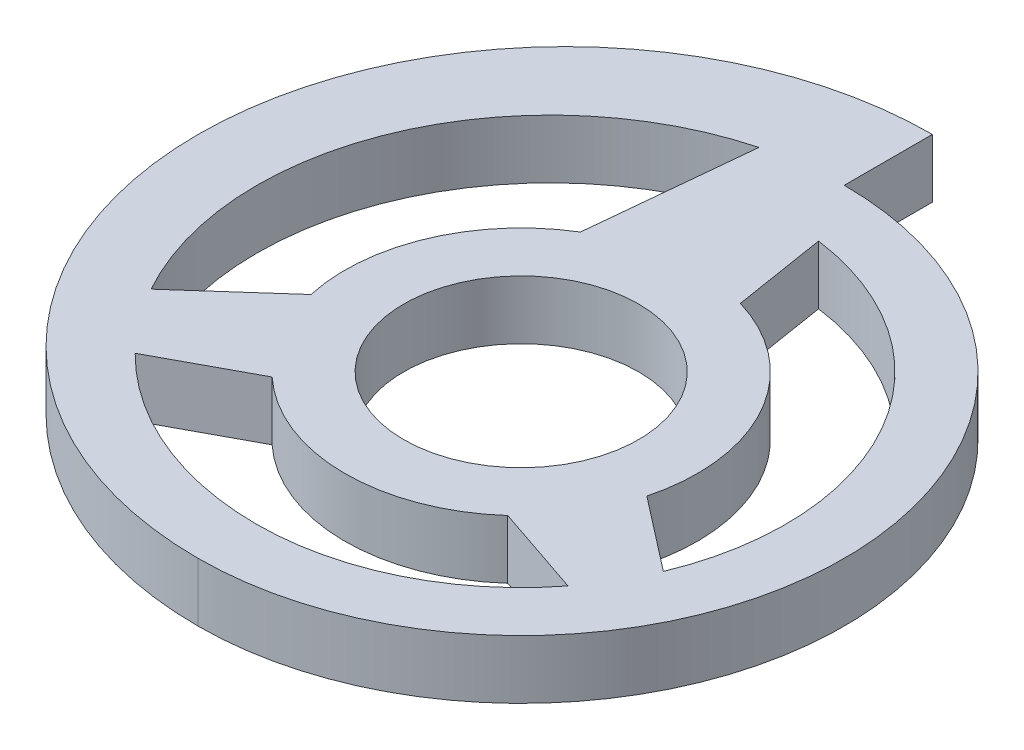
SolidWorks part; units mm, degrees
ref_plane "Front Plane" through (0, 0, 0) normal (0, 0, 1) x (1, 0, 0)
ref_plane "Top Plane" through (0, 0, 0) normal (0, 1, 0) x (1, 0, 0)
ref_plane "Right Plane" through (0, 0, 0) normal (1, 0, 0) x (0, 0, -1)
other "Center of Mass"
sketch "Sketch1" plane through (0, 0, 0) normal (0, 1, 0) x (1, 0, 0)
  line L0 (0, 70) -> (0, 55)
  line L1 (6.0433, 44.5326) -> (8.5696, 28.75)
  line L5 (-35.5895, -30.1196) -> (-20.4365, -21.9624)
  line L6 (-12.8373, 53.3239) -> (-15.5632, 25.6473)
  line L7 (-43.6898, -19.3146) -> (-29.2885, -6.4949)
  line L10 (6.0433, 44.5326) -> (6.0059, 44.5974)
  line L18 (20.041, -22.324) -> (35.5578, -27.5797)
  line L20 (29.0159, -7.6207) -> (41.532, -17.3233)
  arc A0 (0, -55) -> (0, 55) centre (0, 0) ccw
  arc A2 (0, -55) -> (0, 70) centre (0, 7.5) cw
  circle A3 centre (0, 0) radius 20
  arc A4 (29.0159, -7.6207) -> (8.5696, 28.75) centre (0, 0) ccw
  arc A6 (0, -45) -> (-35.5895, -30.1196) centre (0, 5) cw
  arc A7 (0, -45) -> (35.5578, -27.5797) centre (0, 0) ccw
  arc A8 (-15.5632, 25.6473) -> (-29.2885, -6.4949) centre (0, 0) ccw
  arc A10 (29.0159, -7.6207) -> (8.5696, 28.75) centre (0, 0) ccw construction
  arc A11 (-20.4365, -21.9624) -> (20.041, -22.324) centre (0, 0) ccw
  arc A12 (41.532, -17.3233) -> (6.0059, 44.5974) centre (0, 0) ccw
  arc A14 (-15.5632, 25.6473) -> (-29.2885, -6.4949) centre (0, 0) ccw construction
  arc A15 (-43.6898, -19.3146) -> (-12.8373, 53.3239) centre (0, 5) cw
extrude "Boss-Extrude2" add sketch "Sketch1" along normal blind 10
